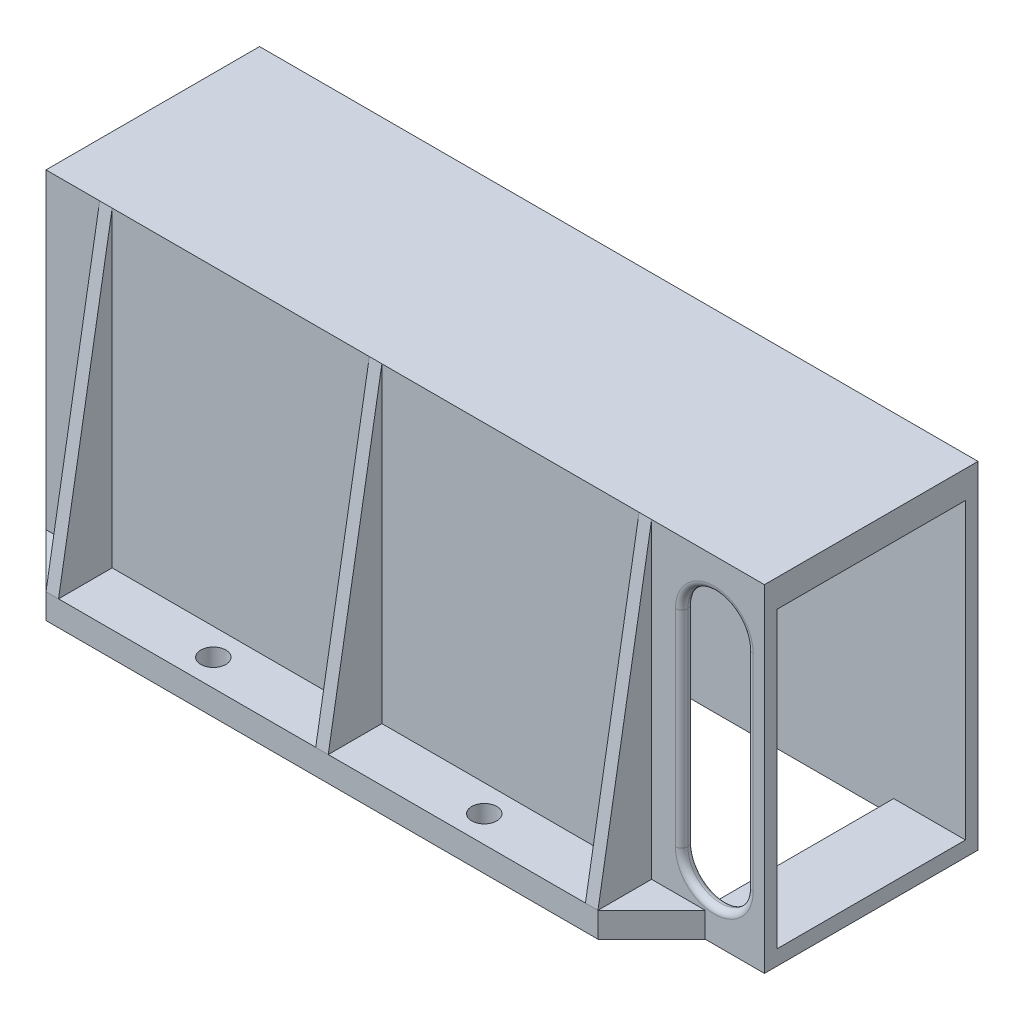
SolidWorks part; units mm, degrees
material "ABS"
ref_plane "Front Plane" through (0, 0, 0) normal (0, 0, 1) x (1, 0, 0)
ref_plane "Top Plane" through (0, 0, 0) normal (0, 1, 0) x (1, 0, 0)
ref_plane "Right Plane" through (0, 0, 0) normal (1, 0, 0) x (0, 0, -1)
sketch "Sketch1" plane through (0, 0, 0) normal (0, 1, 0) x (1, 0, 0)
  line L0 (-83.425, 27.025) -> (83.425, 27.025)
  line L1 (-80.25, -23.85) -> (80.25, -23.85)
  line L2 (-80.25, -23.85) -> (-80.25, 23.85)
  line L3 (-80.25, 23.85) -> (80.25, 23.85)
  line L4 (80.25, -23.85) -> (80.25, 23.85)
  line L5 (-80.25, -23.85) -> (80.25, 23.85) construction
  line L6 (-80.25, 23.85) -> (80.25, -23.85) construction
  line L7 (83.425, -27.025) -> (83.425, 27.025)
  line L8 (-83.425, -27.025) -> (83.425, -27.025)
  line L9 (-83.425, -27.025) -> (-83.425, 27.025)
  point P0 (0, 0)
  dimension "D1" = 160.5
  dimension "D2" = 47.7
  dimension "D3" = 3.175
extrude "Boss-Extrude1" add sketch "Sketch1" along normal blind 3.81
sketch "Sketch2" plane through (0, 3.81, 0) normal (0, 1, 0) x (1, 0, 0)
  line L0 (-83.425, 27.025) -> (83.425, 27.025)
  line L1 (83.425, -27.025) -> (83.425, 27.025) construction
  line L2 (83.425, 27.025) -> (-83.425, 27.025) construction
  line L4 (80.25, 23.85) -> (-80.25, 23.85)
  line L5 (-80.25, 23.85) -> (-80.25, -23.85)
  line L6 (-80.25, -23.85) -> (80.25, -23.85)
  line L8 (83.425, -27.025) -> (-83.425, -27.025)
  line L9 (-83.425, -27.025) -> (-83.425, 27.025)
  line L10 (80.25, 23.85) -> (83.425, 23.85)
  line L11 (83.425, 23.85) -> (83.425, 27.025)
  line L12 (80.25, -23.85) -> (83.425, -23.85)
  line L13 (83.425, -23.85) -> (83.425, -27.025)
extrude "Boss-Extrude2" add sketch "Sketch2" along normal blind 78.232
sketch "Sketch3" plane through (0, 82.042, 0) normal (0, 1, 0) x (1, 0, 0)
  line L0 (83.425, 27.025) -> (83.425, -27.025)
  line L1 (-83.425, 27.025) -> (83.425, 27.025)
  line L2 (-83.425, 27.025) -> (-83.425, -27.025)
  line L5 (83.425, -27.025) -> (-83.425, -27.025)
extrude "Boss-Extrude5" add sketch "Sketch3" along normal blind 3.175 contours L1 L0 L5 L2
sketch "Sketch4" plane through (0, 82.042, 0) normal (0, -1, 0) x (1, 0, 0)
  line L0 (80.25, 27.025) -> (83.425, 27.025)
  line L3 (83.425, -27.025) -> (80.25, -27.025)
  line L4 (80.25, 27.025) -> (80.25, -27.025)
  line L5 (83.425, 27.025) -> (83.425, -27.025)
extrude "Boss-Extrude6" add sketch "Sketch4" along normal blind 3.81
sketch "Sketch5" plane through (0, 0, 0) normal (0, 1, 0) x (1, 0, 0)
  line L0 (-83.425, -27.025) -> (83.425, -27.025)
  line L1 (83.425, -27.025) -> (69.85, -40.6)
  line L2 (69.85, -40.6) -> (-69.85, -40.6)
  line L3 (-69.85, -40.6) -> (-83.425, -27.025)
  line L4 (-83.425, 0) -> (83.425, 0) construction
  line L5 (-83.425, 27.025) -> (-83.425, -27.025) construction
  line L6 (83.425, 27.025) -> (83.425, -27.025) construction
  line L7 (-69.85, 40.6) -> (-83.425, 27.025)
  line L8 (69.85, 40.6) -> (-69.85, 40.6)
  line L9 (83.425, 27.025) -> (69.85, 40.6)
  line L10 (-83.425, 27.025) -> (83.425, 27.025)
  dimension "D1" = 45
  dimension "D2" = 45
  dimension "D3" = 139.7
extrude "Boss-Extrude7" add sketch "Sketch5" along normal blind 6.35
ref_plane "Plane1" through (-69.85, 0, 0) normal (-1, 0, 0) x (0, 0, 1)
sketch "Sketch6" plane through (-69.85, 0, 0) normal (-1, 0, 0) x (0, 0, 1)
  line L0 (27.025, 85.217) -> (27.025, 6.35)
  line L1 (27.025, 6.35) -> (40.6, 6.35)
  line L2 (0, 85.217) -> (0, 0) construction
  line L3 (-27.025, 85.217) -> (27.025, 85.217) construction
  line L4 (-27.025, 0) -> (27.025, 0) construction
  line L5 (27.025, 85.217) -> (40.6, 6.35)
  line L6 (-27.025, 85.217) -> (-40.6, 6.35)
  line L7 (-27.025, 6.35) -> (-40.6, 6.35)
  line L8 (-27.025, 85.217) -> (-27.025, 6.35)
extrude "Boss-Extrude9" add sketch "Sketch6" against normal blind 3.175
ref_plane "Plane2" through (69.85, 0, 0) normal (1, 0, 0) x (0, 0, -1)
sketch "Sketch7" plane through (69.85, 0, 0) normal (1, 0, 0) x (0, 0, -1)
  line L0 (-27.025, 85.217) -> (-27.025, 6.35)
  line L1 (-27.025, 6.35) -> (-40.6, 6.35)
  line L2 (-40.6, 6.35) -> (-27.025, 85.217)
  line L3 (0, 0) -> (0, 79.375) construction
  line L4 (40.6, 6.35) -> (27.025, 85.217)
  line L5 (27.025, 6.35) -> (40.6, 6.35)
  line L6 (27.025, 85.217) -> (27.025, 6.35)
extrude "Boss-Extrude10" add sketch "Sketch7" against normal blind 3.175
sketch "Sketch8" plane through (0, 6.35, 0) normal (0, 1, 0) x (1, 0, 0)
  line L0 (-83.425, 0) -> (83.425, 0) construction
  line L1 (66.675, -27.025) -> (-66.675, -27.025) construction
  line L3 (-83.425, 27.025) -> (-83.425, -27.025) construction
  line L4 (83.425, 27.025) -> (83.425, -27.025) construction
  line L5 (0, 40.6) -> (0, -40.6) construction
  line L6 (66.675, 40.6) -> (-66.675, 40.6) construction
  line L7 (-66.675, -40.6) -> (66.675, -40.6) construction
  circle A0 centre (-34.29, -33.8125) radius 3.175
  circle A1 centre (34.29, -33.8125) radius 3.175
  circle A2 centre (34.29, 33.8125) radius 3.175
  circle A3 centre (-34.29, 33.8125) radius 3.175
  dimension "D3" = 6.35
  dimension "D1" = 6.7875
  dimension "D2" = 34.29
extrude "Cut-Extrude1" cut sketch "Sketch8" against normal through all
sketch "Sketch11" plane through (0, 0, 0) normal (1, 0, 0) x (0, 0, -1)
  line L0 (-27.025, 85.217) -> (-27.025, 6.35)
  line L1 (-27.025, 6.35) -> (-40.6, 6.35)
  line L2 (-40.6, 6.35) -> (-27.025, 85.217)
  line L3 (0, 85.217) -> (0, 0) construction
  line L4 (27.025, 85.217) -> (-27.025, 85.217) construction
  line L5 (40.6, 6.35) -> (27.025, 85.217)
  line L6 (27.025, 6.35) -> (40.6, 6.35)
  line L7 (27.025, 85.217) -> (27.025, 6.35)
extrude "Boss-Extrude11" add sketch "Sketch11" along normal blind 1.5875 and the other way blind 1.5875
ref_plane "Plane4" through (98.411, 0, 0) normal (1, 0, 0) x (0, 0, -1)
sketch "Sketch14" plane through (98.411, 0, 0) normal (1, 0, 0) x (0, 0, -1)
  line L1 (-27.025, 85.217) -> (27.025, 85.217)
  line L2 (-27.025, 85.217) -> (-27.025, 0)
  line L3 (-27.025, 0) -> (27.025, 0)
  line L4 (27.025, 85.217) -> (27.025, 0)
  line L5 (-23.85, 78.232) -> (23.85, 78.232)
  line L6 (-23.85, 78.232) -> (-23.85, 3.81)
  line L7 (-23.85, 3.81) -> (23.85, 3.81)
  line L8 (23.85, 78.232) -> (23.85, 3.81)
extrude "Boss-Extrude13" add sketch "Sketch14" against normal up to surface (14.986 mm away) up to face at (83.425, 41.021, 0)
sketch "Sketch15" plane through (0, 0, -27.025) normal (0, 0, -1) x (-1, 0, 0)
  line L0 (-69.85, 85.217) -> (-98.411, 85.217) construction
  line L1 (-83.425, 0) -> (-98.411, 0) construction
  line L2 (-98.411, 0) -> (-98.411, 85.217) construction
  line L3 (-93.966, 68.707) -> (-93.966, 16.51)
  line L4 (-77.456, 68.707) -> (-77.456, 16.51)
  arc A0 (-77.456, 68.707) -> (-93.966, 68.707) centre (-85.711, 68.707) ccw
  arc A1 (-93.966, 16.51) -> (-77.456, 16.51) centre (-85.711, 16.51) ccw
  dimension "D1" = 16.51
  dimension "D2" = 16.51
  dimension "D3" = 12.7
  dimension "D4" = 16.51
extrude "Cut-Extrude2" cut sketch "Sketch15" against normal through all
sketch "Sketch16" plane through (0, 82.042, 0) normal (0, -1, 0) x (1, 0, 0)
  line L1 (-80.25, 23.85) -> (80.25, 23.85)
  line L2 (-80.25, 23.85) -> (-80.25, -23.85)
  line L3 (-80.25, -23.85) -> (80.25, -23.85)
  line L4 (80.25, 23.85) -> (80.25, -23.85)
extrude "Cut-Extrude3" cut sketch "Sketch16" against normal blind 1.5875
sketch "Sketch17" plane through (0, 0, -27.025) normal (0, 0, -1) x (-1, 0, 0)
  line L1 (-95.0673, 7.97) -> (-76.3547, 7.97)
  line L2 (-95.0673, 7.97) -> (-95.0673, 77.247)
  line L3 (-95.0673, 77.247) -> (-76.3547, 77.247)
  line L4 (-76.3547, 7.97) -> (-76.3547, 77.247)
  line L5 (-95.0673, 7.97) -> (-76.3547, 77.247) construction
  line L6 (-95.0673, 77.247) -> (-76.3547, 7.97) construction
  point P0 (-85.711, 42.6085)
extrude "Boss-Extrude14" add sketch "Sketch17" against normal up to surface (3.175 mm away) up to face at (85.711, 42.6085, -23.85)
fillet "Fillet1" radius 1.5875 8 edges at (85.711, 8.255, 23.85) (93.966, 42.6085, 23.85) (85.711, 76.962, 23.85) (85.711, 76.962, 27.025) (77.456, 42.6085, 27.025) (85.711, 8.255, 27.025) (77.456, 42.6085, 23.85) (93.966, 42.6085, 27.025)
